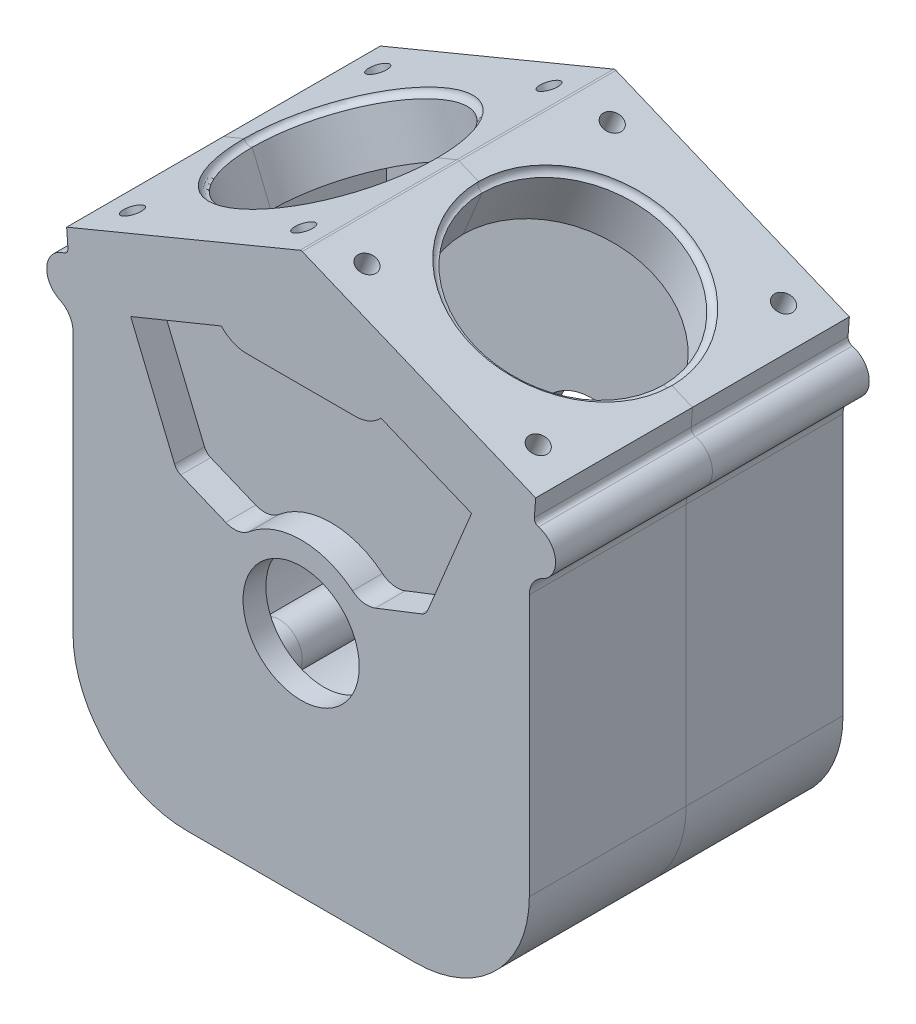
SolidWorks part; units mm, degrees
ref_plane "Front Plane" through (0, 0, 0) normal (0, 0, 1) x (1, 0, 0)
ref_plane "Top Plane" through (0, 0, 0) normal (0, 1, 0) x (1, 0, 0)
ref_plane "Right Plane" through (0, 0, 0) normal (1, 0, 0) x (0, 0, -1)
sketch "Sketch1" plane through (0, 0, 0) normal (0, 0, 1) x (1, 0, 0)
  line L0 (0, 0) -> (-126.0705, 304.361) construction
  line L1 (0, 0) -> (0, 746.2278) construction
  line L2 (-179.6035, 282.1869) -> (-72.5374, 326.5351) construction
  line L3 (-72.5374, 326.5351) -> (-60.8041, 331.3952) construction
  line L4 (-179.6035, 282.1869) -> (-191.3368, 277.3268) construction
  line L5 (-60.8041, 331.3952) -> (0, 184.601) construction
  line L6 (-72.5374, 326.5351) -> (0, 151.4143) construction
  line L7 (-191.3368, 277.3268) -> (-130.5326, 130.5326) construction
  line L8 (-179.6035, 282.1869) -> (-118.7994, 135.3927) construction
  line L9 (0, 184.601) -> (-130.5326, 130.5326) construction
  line L11 (-132.4404, 127.9947) -> (-127, 92.4608) construction
  line L12 (-118.7994, 135.3927) -> (-107.0661, 107.0661) construction
  line L13 (-114.3, 124.5303) -> (-114.3, 0) construction
  line L14 (-114.3, 0) -> (-114.3, -63.5) construction
  line L15 (-63.5, -114.3) -> (63.5, -114.3) construction
  line L16 (-63.5, -127) -> (63.5, -127)
  line L19 (0, 151.4143) -> (-107.0661, 107.0661) construction
  line L20 (-127, 82.0146) -> (-127, -63.5)
  line L21 (-107.0661, 107.0661) -> (-114.3, 124.5303) construction
  line L22 (-130.5326, 130.5326) -> (0, 184.601)
  line L26 (130.5326, 130.5326) -> (0, 184.601)
  line L28 (127, 82.0146) -> (127, -63.5)
  line L29 (-129.8023, 120.5978) -> (-130.5326, 130.5326)
  line L30 (130.5326, 130.5326) -> (129.8023, 120.5978)
  circle A0 centre (0, 0) radius 82.55 construction
  arc A1 (-132.1594, 117.2949) -> (-134.311, 93.5145) centre (-128.922, 105.0145) ccw
  circle A2 centre (0, 0) radius 114.3 construction
  arc A7 (-129.8023, 120.5978) -> (-132.1594, 117.2949) centre (-132.9687, 120.365) cw
  arc A13 (132.1594, 117.2949) -> (134.311, 93.5145) centre (128.922, 105.0145) cw
  arc A14 (129.8023, 120.5978) -> (132.1594, 117.2949) centre (132.9687, 120.365) ccw
  arc A15 (-134.311, 93.5145) -> (-127, 82.0146) centre (-139.7, 82.0146) cw
  arc A16 (127, 82.0146) -> (134.311, 93.5145) centre (139.7, 82.0146) cw
  arc A17 (-114.3, -63.5) -> (-63.5, -114.3) centre (-63.5, -63.5) ccw construction
  arc A18 (-127, -63.5) -> (-63.5, -127) centre (-63.5, -63.5) ccw
  arc A19 (127, -63.5) -> (63.5, -127) centre (63.5, -63.5) cw
  point P8 (-126.0705, 304.361)
  point P21 (0, -114.3)
  point P24 (0, -127)
  point P49 (127, 92.4608)
  dimension "D1" = 165.1
  dimension "D7" = 12.7
  dimension "D11" = 31.75
  dimension "D12" = 50.8
  dimension "D13" = 12.7
  dimension "D14" = 4.5
  dimension "D15" = 3.175
  dimension "D16" = 9.9348
  dimension "D10" = 12.7
  dimension "D2" = 22.5
  dimension "D3" = 329.438
  dimension "D4" = 115.8875
  dimension "D5" = 12.7
  dimension "D6" = 3.175
  dimension "D8" = 12.7
  dimension "D9" = 12.7
extrude "Boss-Extrude1" add sketch "Sketch1" along normal mid plane 174.625
sketch "Sketch3" plane through (0, 0, 0) normal (0, 0, 1) x (1, 0, 0)
  line L7 (12.7, -114.3) -> (63.5, -114.3)
  line L9 (-12.7, -114.3) -> (-63.5, -114.3)
  line L10 (-108.4013, -108.4013) -> (0, 0) construction
  line L11 (114.3, -63.5) -> (114.3, 104.0697)
  line L12 (-12.7, -114.3) -> (12.7, -114.3)
  line L13 (-118.7994, 135.3927) -> (-114.3, 124.5303) construction
  line L15 (0, 151.4143) -> (-114.3, 104.0697)
  line L16 (-114.3, 104.0697) -> (-114.3, -63.5)
  line L19 (127, -63.5) -> (127, 82.0146)
  line L20 (127, -63.5) -> (127, 82.0146)
  line L22 (0, 184.601) -> (0, 0) construction
  line L23 (-11.7333, 179.7409) -> (0, 151.4143) construction
  line L25 (130.5326, 130.5326) -> (0, 184.601)
  line L26 (0, 184.601) -> (-130.5326, 130.5326)
  line L27 (-130.5326, 130.5326) -> (-129.8023, 120.5978)
  line L28 (-127, 82.0146) -> (-127, -63.5)
  line L29 (-63.5, -127) -> (63.5, -127)
  line L31 (129.8023, 120.5978) -> (130.5326, 130.5326)
  line L32 (130.5326, 130.5326) -> (0, 184.601) construction
  line L33 (0, 184.601) -> (-130.5326, 130.5326) construction
  line L35 (-127, 82.0146) -> (-127, -63.5) construction
  line L36 (-63.5, -127) -> (63.5, -127) construction
  line L38 (129.8023, 120.5978) -> (130.5326, 130.5326) construction
  line L39 (0, 151.4143) -> (114.3, 104.0697)
  line L42 (-130.5326, 130.5326) -> (-129.8023, 120.5978)
  arc A5 (-12.7, -114.3) -> (12.7, -114.3) centre (0, -114.3) cw construction
  arc A6 (-63.5, -114.3) -> (-89.3887, -107.2083) centre (-63.5, -63.5) cw
  arc A8 (63.5, -114.3) -> (89.3887, -107.2083) centre (63.5, -63.5) ccw
  arc A9 (-89.3887, -107.2083) -> (-107.2083, -89.3887) centre (-99.421, -99.421) ccw
  arc A11 (-107.2083, -89.3887) -> (-114.3, -63.5) centre (-63.5, -63.5) cw
  arc A12 (89.3887, -107.2083) -> (107.2083, -89.3887) centre (99.421, -99.421) cw
  arc A13 (107.2083, -89.3887) -> (114.3, -63.5) centre (63.5, -63.5) ccw
  arc A16 (-127, -63.5) -> (-63.5, -127) centre (-63.5, -63.5) ccw
  arc A17 (-132.1594, 117.2949) -> (-129.8023, 120.5978) centre (-132.9687, 120.365) ccw
  arc A18 (-132.1594, 117.2949) -> (-134.311, 93.5145) centre (-128.922, 105.0145) ccw
  arc A19 (-127, 82.0146) -> (-134.311, 93.5145) centre (-139.7, 82.0146) ccw
  arc A20 (-127, -63.5) -> (-63.5, -127) centre (-63.5, -63.5) ccw
  arc A21 (63.5, -127) -> (127, -63.5) centre (63.5, -63.5) ccw
  arc A22 (134.311, 93.5145) -> (127, 82.0146) centre (139.7, 82.0146) ccw
  arc A23 (134.311, 93.5145) -> (132.1594, 117.2949) centre (128.922, 105.0145) ccw
  arc A24 (129.8023, 120.5978) -> (132.1594, 117.2949) centre (132.9687, 120.365) ccw
  arc A25 (-132.1594, 117.2949) -> (-129.8023, 120.5978) centre (-132.9687, 120.365) ccw construction
  arc A26 (-132.1594, 117.2949) -> (-134.311, 93.5145) centre (-128.922, 105.0145) ccw construction
  arc A27 (-127, 82.0146) -> (-134.311, 93.5145) centre (-139.7, 82.0146) ccw construction
  arc A30 (134.311, 93.5145) -> (127, 82.0146) centre (139.7, 82.0146) ccw construction
  arc A31 (134.311, 93.5145) -> (132.1594, 117.2949) centre (128.922, 105.0145) ccw construction
  arc A32 (129.8023, 120.5978) -> (132.1594, 117.2949) centre (132.9687, 120.365) ccw construction
  arc A33 (63.5, -127) -> (127, -63.5) centre (63.5, -63.5) ccw
  point P42 (0, 0)
  point P43 (-114.2784, -64.9796)
  dimension "D3" = 25.4
  dimension "D4" = 12.7
  dimension "D5" = 12.7
  dimension "D8" = 12.7
  dimension "D1" = 0
  dimension "D2" = 12.7
  dimension "D6" = 12.7
extrude "Cut-Extrude1" cut sketch "Sketch3" against normal mid plane 149.225 contours A5 L7 L11 L39 region at (0, 10.2904, 0)
sketch "Sketch4" plane through (-65.2663, 157.5668, 0) normal (-0.3827, 0.9239, 0) x (0.9239, 0.3827, 0)
  circle A0 centre (0, 0) radius 54.7687
  dimension "D1" = 109.5375
extrude "Cut-Extrude2" cut sketch "Sketch4" against normal up to next
sketch "Sketch5" plane through (0, 0, 87.3125) normal (0, 0, 1) x (1, 0, 0)
  circle A0 centre (0, 0) radius 32.3456
  dimension "D1" = 64.6913
extrude "Cut-Extrude3" cut sketch "Sketch5" against normal through all
sketch "Sketch6" plane through (0, 0, 87.3125) normal (0, 0, 1) x (1, 0, 0)
  line L0 (0, 151.4143) -> (0, 0) construction
  line L1 (-103.1682, 108.6806) -> (-76.319, 43.8607)
  line L2 (-34.246, 22.4073) -> (-69.4458, 36.9875)
  line L3 (34.246, 22.4073) -> (69.4458, 36.9875)
  line L4 (103.1682, 108.6806) -> (76.319, 43.8607)
  line L8 (-106.8975, 107.1359) -> (-106.8975, -114.3) construction
  line L9 (-127, 82.0146) -> (-127, -63.5) construction
  line L10 (106.8975, 107.1359) -> (106.8975, -114.3) construction
  line L11 (0, 151.4143) -> (0, 184.601) construction
  line L12 (0, 151.4143) -> (-11.7333, 179.7409) construction
  line L13 (0, 184.601) -> (-130.5326, 130.5326) construction
  line L14 (-106.8975, 107.1359) -> (-118.6307, 135.4626) construction
  line L18 (0, 151.4143) -> (-106.8975, 107.1359) construction
  line L19 (106.8975, 107.1359) -> (0, 151.4143) construction
  line L24 (-30.18, 126.0143) -> (30.18, 126.0143)
  line L25 (-42.0971, 133.9771) -> (0, 32.3456) construction
  line L26 (-103.1682, 108.6806) -> (-42.0971, 133.9771)
  line L27 (103.1682, 108.6806) -> (42.0971, 133.9771)
  circle A0 centre (0, 0) radius 32.3456 construction
  circle A1 centre (0, 0) radius 32.3456 construction
  arc A2 (-21.1009, 24.5151) -> (21.1009, 24.5151) centre (0, 0) cw
  arc A3 (34.246, 22.4073) -> (21.1009, 24.5151) centre (29.3859, 34.1406) cw
  arc A4 (-34.246, 22.4073) -> (-21.1009, 24.5151) centre (-29.3859, 34.1406) ccw
  arc A5 (-76.319, 43.8607) -> (-69.4458, 36.9875) centre (-64.5857, 48.7208) ccw
  arc A7 (30.18, 126.0143) -> (42.0971, 133.9771) centre (30.18, 138.9134) ccw
  arc A8 (-42.0971, 133.9771) -> (-30.18, 126.0143) centre (-30.18, 138.9134) ccw
  arc A14 (69.4458, 36.9875) -> (76.319, 43.8607) centre (64.5857, 48.7208) ccw
  point P10 (0, 126.0143)
  point P23 (26.1407, 19.05)
  point P28 (-26.1407, 19.05)
  point P31 (-74.3059, 39.0007)
  point P34 (74.3059, 39.0007)
  dimension "D3" = 12.7
  dimension "D1" = 12.7
  dimension "D2" = 19.05
  dimension "D4" = 25.4
  dimension "D6" = 38.1
extrude "Boss-Extrude2" add sketch "Sketch6" against normal blind 16.6687 from surface starting at face at (32.3456, 0, 74.6125)
sketch "Sketch7" plane through (0, 0, 87.3125) normal (0, 0, 1) x (1, 0, 0)
  line L10 (41.287, 32.7885) -> (66.8989, 42.8072)
  line L11 (70.4523, 46.2908) -> (94.8808, 105.2663)
  line L18 (-94.8808, 105.2663) -> (-70.4523, 46.2908)
  line L19 (-67.0157, 42.8542) -> (-41.9935, 32.4896)
  line L30 (-69.4458, 36.9875) -> (-34.246, 22.4073)
  line L31 (-103.1682, 108.6806) -> (-76.319, 43.8607)
  line L32 (103.1682, 108.6806) -> (42.0971, 133.9771)
  line L37 (-30.18, 119.6643) -> (30.18, 119.6643)
  line L38 (76.319, 43.8607) -> (103.1682, 108.6806)
  line L39 (34.246, 22.4073) -> (69.4458, 36.9875)
  line L40 (-69.4458, 36.9875) -> (-34.246, 22.4073)
  line L41 (-103.1682, 108.6806) -> (-76.319, 43.8607)
  line L48 (76.319, 43.8607) -> (103.1682, 108.6806)
  line L49 (34.246, 22.4073) -> (69.4458, 36.9875)
  line L50 (-94.8808, 105.2663) -> (-44.4009, 125.9407)
  line L51 (44.4009, 125.9407) -> (94.8808, 105.2663)
  line L57 (30.18, 126.0143) -> (-30.18, 126.0143)
  line L58 (30.18, 126.0143) -> (-30.18, 126.0143)
  line L68 (103.1682, 108.6806) -> (42.0971, 133.9771)
  line L70 (-42.0971, 133.9771) -> (-103.1682, 108.6806)
  line L71 (-42.0971, 133.9771) -> (-103.1682, 108.6806)
  arc A1 (66.8989, 42.8072) -> (70.4523, 46.2908) centre (64.5857, 48.7208) ccw
  arc A6 (-70.4523, 46.2908) -> (-67.0157, 42.8542) centre (-64.5857, 48.7208) ccw
  arc A7 (-28.9667, 34.497) -> (28.5977, 34.8034) centre (0, 0) cw
  arc A8 (41.287, 32.7885) -> (28.5977, 34.8034) centre (36.6605, 44.6158) cw
  arc A9 (-41.9935, 32.4896) -> (-28.9667, 34.497) centre (-37.1334, 44.2229) ccw
  arc A10 (-76.319, 43.8607) -> (-69.4458, 36.9875) centre (-64.5857, 48.7208) ccw
  arc A11 (-44.4009, 125.9407) -> (-30.18, 119.6643) centre (-30.18, 138.9134) ccw
  arc A12 (-42.0971, 133.9771) -> (-30.18, 126.0143) centre (-30.18, 138.9134) ccw
  arc A13 (30.18, 119.6643) -> (44.4009, 125.9407) centre (30.18, 138.9134) ccw
  arc A14 (69.4458, 36.9875) -> (76.319, 43.8607) centre (64.5857, 48.7208) ccw
  arc A15 (21.1009, 24.5151) -> (34.246, 22.4073) centre (29.3859, 34.1406) ccw
  arc A16 (21.1009, 24.5151) -> (-21.1009, 24.5151) centre (0, 0) ccw
  arc A17 (-34.246, 22.4073) -> (-21.1009, 24.5151) centre (-29.3859, 34.1406) ccw
  arc A18 (-76.319, 43.8607) -> (-69.4458, 36.9875) centre (-64.5857, 48.7208) ccw
  arc A22 (69.4458, 36.9875) -> (76.319, 43.8607) centre (64.5857, 48.7208) ccw
  arc A23 (21.1009, 24.5151) -> (34.246, 22.4073) centre (29.3859, 34.1406) ccw
  arc A24 (21.1009, 24.5151) -> (-21.1009, 24.5151) centre (0, 0) ccw
  arc A25 (-34.246, 22.4073) -> (-21.1009, 24.5151) centre (-29.3859, 34.1406) ccw
  arc A37 (-42.0971, 133.9771) -> (-30.18, 126.0143) centre (-30.18, 138.9134) ccw
  arc A38 (30.18, 126.0143) -> (42.0971, 133.9771) centre (30.18, 138.9134) ccw
  arc A39 (30.18, 126.0143) -> (42.0971, 133.9771) centre (30.18, 138.9134) ccw
  point P8 (0, 126.0143)
  point P10 (0, 119.6643)
  dimension "D2" = 12.7
  dimension "D5" = 6.35
  dimension "D7" = 12.7
  dimension "D4" = 6.35
  dimension "D6" = 1.136
  dimension "D11" = 6.35
  dimension "D1" = 0
extrude "Cut-Extrude5" cut sketch "Sketch7" against normal offset from surface (16.6687 mm away) 12.7 contours L19 A9 A7 A8 L10 A1 L11 L18 A6 region at (-0.0395, 80.6799, 87.3125) up to face at (0, 70.8581, 57.9438)
hole_wizard "Tap Drill for 1/2-13 Tap2" positions "Sketch10" profile "Sketch11" hole size "1/2-13" standard "ANSI Inch"
sketch "Sketch10" plane through (-65.2663, 157.5668, 0) normal (-0.3827, 0.9239, 0) x (0.9239, 0.3827, 0)
  line L1 (-51.5937, -68.2625) -> (51.5937, -68.2625)
  line L2 (-51.5937, -68.2625) -> (-51.5937, 68.2625)
  line L3 (-51.5937, 68.2625) -> (51.5937, 68.2625)
  line L4 (51.5937, -68.2625) -> (51.5937, 68.2625)
  line L6 (70.6438, 87.3125) -> (-70.6437, 87.3125) construction
  line L7 (-70.6437, -87.3125) -> (-70.6437, 87.3125) construction
  circle A0 centre (0, 0) radius 54.7687 construction
  circle A1 centre (0, 0) radius 54.7687
  point P0 (-51.5937, 68.2625)
  point P2 (51.5937, 68.2625)
  point P4 (51.5937, -68.2625)
  point P6 (-51.5937, -68.2625)
  point P43 (-51.5937, 0)
  point P44 (0, 68.2625)
  dimension "D1" = 19.05
  dimension "D2" = 19.05
sketch "Sketch11" plane through (-112.9327, 137.8227, -68.2625) normal (0, 0, 1) x (-0.9239, -0.3827, 0)
  line L0 (0, 0) -> (0, 22.2695)
  line L1 (0, 22.2695) -> (5.3581, 19.05)
  line L2 (5.3581, 19.05) -> (5.3581, 0)
  line L5 (5.3581, 0) -> (0, 0)
  line L10 (0, 22.2695) -> (-5.3581, 19.05) construction
  line L11 (0, -6.35) -> (0, 107.95) construction
  dimension "Hole Dia." = 10.7163
  dimension "Hole Depth" = 19.05
  dimension "Drill Angle" = 118
sketch "Sketch12" plane through (-65.2663, 157.5668, 0) normal (-0.3827, 0.9239, 0) x (0.9239, 0.3827, 0)
  circle A0 centre (0, 0) radius 58.2613
  circle A1 centre (0, 0) radius 54.7687 construction
  circle A2 centre (0, 0) radius 54.7687
  dimension "D1" = 3.4925
extrude "Cut-Extrude6" cut sketch "Sketch12" against normal blind 3.4925
fillet "Fillet3" radius 1.5875 1 edges at (0, 184.601, 0)
fillet "Fillet4" radius 3.4925 1 edges at (-117.7562, 132.0446, 0)
mirror "Mirror2" about plane through (0, 0, 0) normal (1, 0, 0) of "Fillet4", "Cut-Extrude2", "Tap Drill for 1/2-13 Tap2", "Cut-Extrude6"
split "Split1" trim tools "Front Plane" bodies to split 117 resulting bodies 109 110
